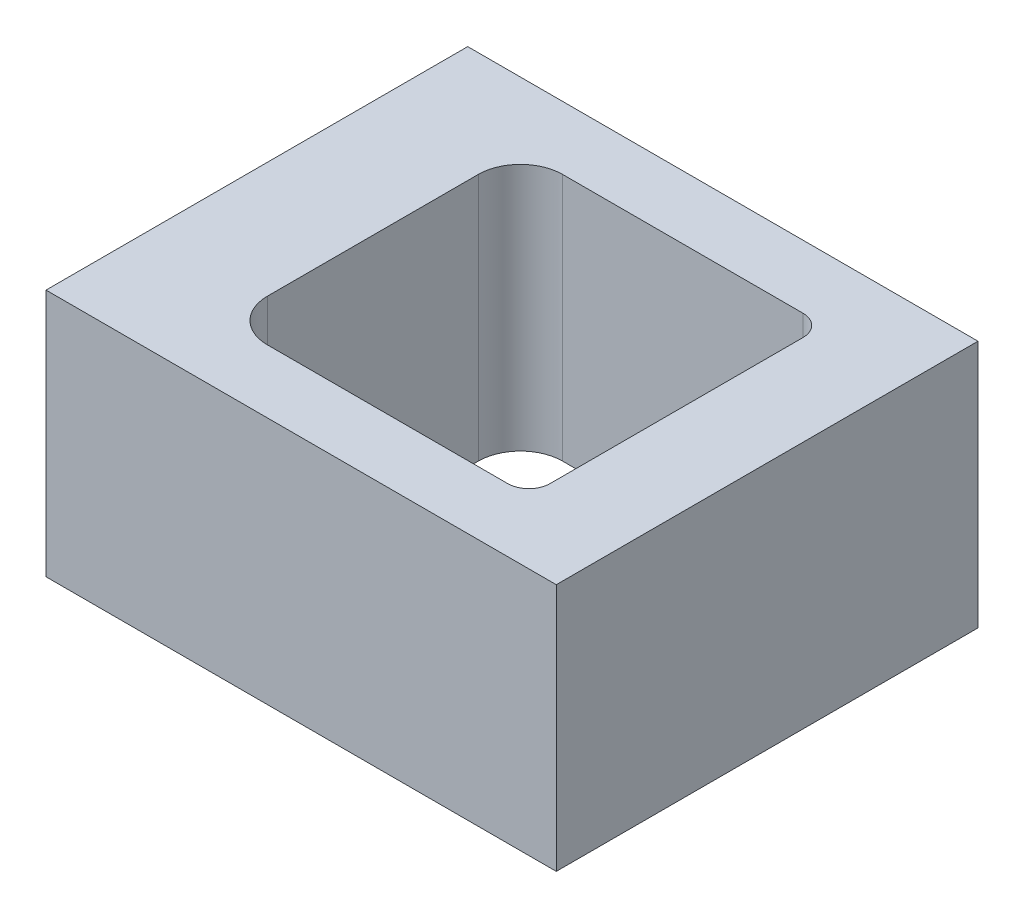
SolidWorks part; units mm, degrees
ref_plane "Front Plane" through (0, 0, 0) normal (0, 0, 1) x (1, 0, 0)
ref_plane "Top Plane" through (0, 0, 0) normal (0, 1, 0) x (1, 0, 0)
ref_plane "Right Plane" through (0, 0, 0) normal (1, 0, 0) x (0, 0, -1)
sketch "Sketch1" plane through (0, 0, 0) normal (0, 1, 0) x (1, 0, 0)
  line L1 (-88.265, -63.5) -> (65.405, -63.5)
  line L2 (-88.265, -63.5) -> (-88.265, 63.5)
  line L3 (-88.265, 63.5) -> (65.405, 63.5)
  line L4 (65.405, -63.5) -> (65.405, 63.5)
  line L5 (-88.265, -63.5) -> (65.405, 63.5) construction
  line L6 (-88.265, 63.5) -> (65.405, -63.5) construction
  line L22 (65.405, 0) -> (38.1, 0) construction
  line L23 (38.1, 38.1) -> (38.1, -38.1) construction
  line L27 (-53.34, 31.75) -> (-53.34, -31.75)
  line L28 (-40.64, -44.45) -> (31.75, -44.45)
  line L29 (38.1, -38.1) -> (38.1, 38.1)
  line L30 (31.75, 44.45) -> (-40.64, 44.45)
  line L31 (-53.34, 31.75) -> (-53.34, -31.75)
  line L32 (-40.64, -44.45) -> (31.75, -44.45)
  line L33 (38.1, -38.1) -> (38.1, 38.1)
  line L34 (31.75, 44.45) -> (-40.64, 44.45)
  arc A28 (-40.64, 44.45) -> (-53.34, 31.75) centre (-40.64, 31.75) ccw
  arc A29 (-40.64, 44.45) -> (-53.34, 31.75) centre (-40.64, 31.75) ccw
  arc A30 (-53.34, -31.75) -> (-40.64, -44.45) centre (-40.64, -31.75) ccw
  arc A31 (-53.34, -31.75) -> (-40.64, -44.45) centre (-40.64, -31.75) ccw
  arc A32 (31.75, -44.45) -> (38.1, -38.1) centre (31.75, -38.1) ccw
  arc A33 (31.75, -44.45) -> (38.1, -38.1) centre (31.75, -38.1) ccw
  arc A34 (38.1, 38.1) -> (31.75, 44.45) centre (31.75, 38.1) ccw
  arc A35 (38.1, 38.1) -> (31.75, 44.45) centre (31.75, 38.1) ccw
  dimension "D1" = 127
  dimension "D2" = 153.67
  dimension "D3" = 0
  dimension "D4" = 27.305
extrude "Boss-Extrude1" add sketch "Sketch1" along normal offset from surface (74.7776 mm away) 73.1774
